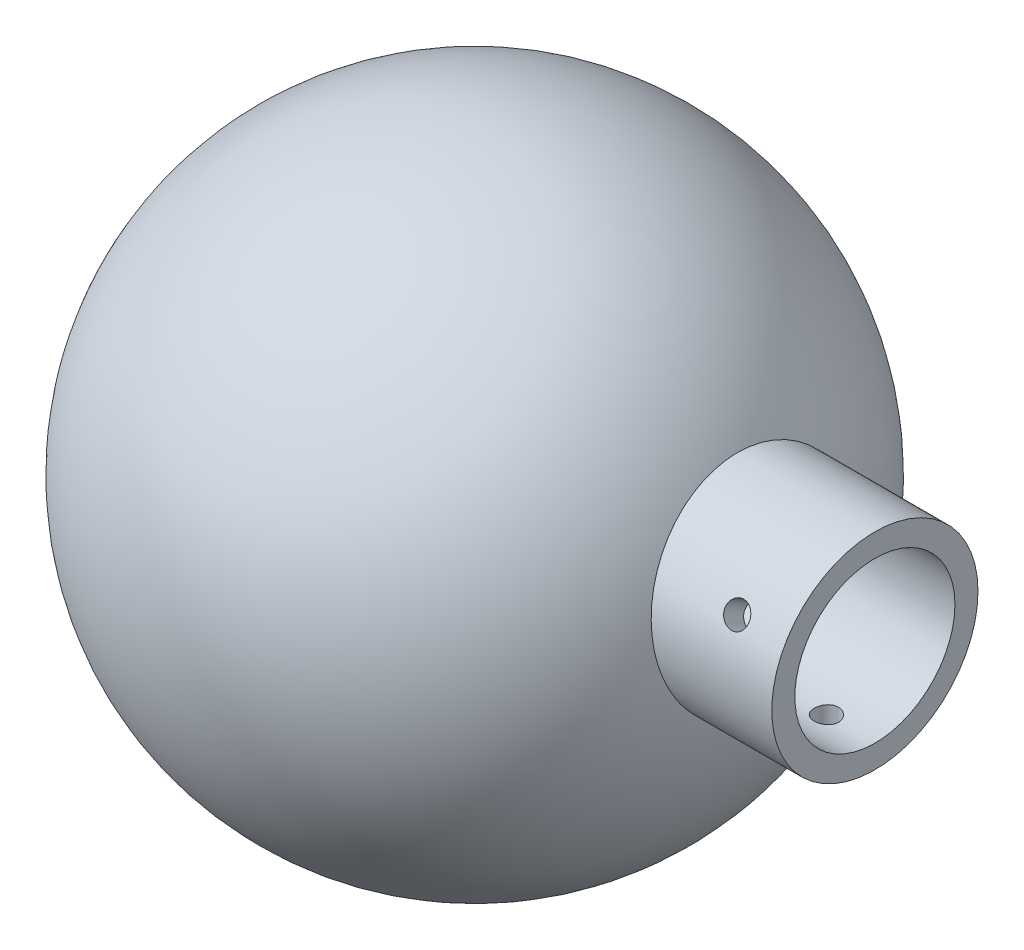
SolidWorks part; units mm, degrees
ref_plane "Front Plane" through (0, 0, 0) normal (0, 0, 1) x (1, 0, 0)
ref_plane "Top Plane" through (0, 0, 0) normal (0, 1, 0) x (1, 0, 0)
ref_plane "Right Plane" through (0, 0, 0) normal (1, 0, 0) x (0, 0, -1)
sketch "Sketch1" plane through (0, 0, 0) normal (0, 0, 1) x (1, 0, 0)
  line L0 (-63.5, 0) -> (-60.96, 0)
  line L1 (60.96, 0) -> (63.5, 0)
  arc A0 (63.5, 0) -> (-63.5, 0) centre (0, 0) ccw
  arc A1 (60.96, 0) -> (-60.96, 0) centre (0, 0) ccw
  dimension "D1" = 63.5
  dimension "D2" = 60.96
revolve "Revolve1" add sketch "Sketch1" angle 360 about L0
sketch "Sketch2" plane through (0, 0, 0) normal (1, 0, 0) x (0, 0, -1)
  line L0 (0, 69.85) -> (0, -69.85) construction
  line L1 (69.85, 0) -> (-69.85, 0) construction
  circle A0 centre (0, 10.0076) radius 21.59
  circle A1 centre (0, 10.0076) radius 16.764
  dimension "D1" = 10.0076
  dimension "D2" = 33.528
  dimension "D3" = 43.18
extrude "Boss-Extrude1" add sketch "Sketch2" along normal blind 83.82 and the other way up to next
extrude "Cut-Extrude3" cut sketch "Sketch2<4>" along normal blind 138.938 contours A1
sketch "Sketch2<4>" plane through (0, 0, 0) normal (1, 0, 0) x (0, 0, -1) same geometry as "Sketch2"
sketch "Sketch4" plane through (0, 0, 0) normal (0, 1, 0) x (1, 0, 0)
  line L0 (-69.85, 0) -> (69.85, 0) construction
  line L1 (83.82, -21.59) -> (83.82, 21.59) construction
  circle A0 centre (73.66, 0) radius 2.54
  dimension "D1" = 10.16
extrude "Cut-Extrude4" cut sketch "Sketch4" against normal blind 138.938
pattern_circular "CirPattern1" count 3 every 120 about axis through (-63.502, 10.0076, 0) along (1, 0, 0) of "Cut-Extrude4"
